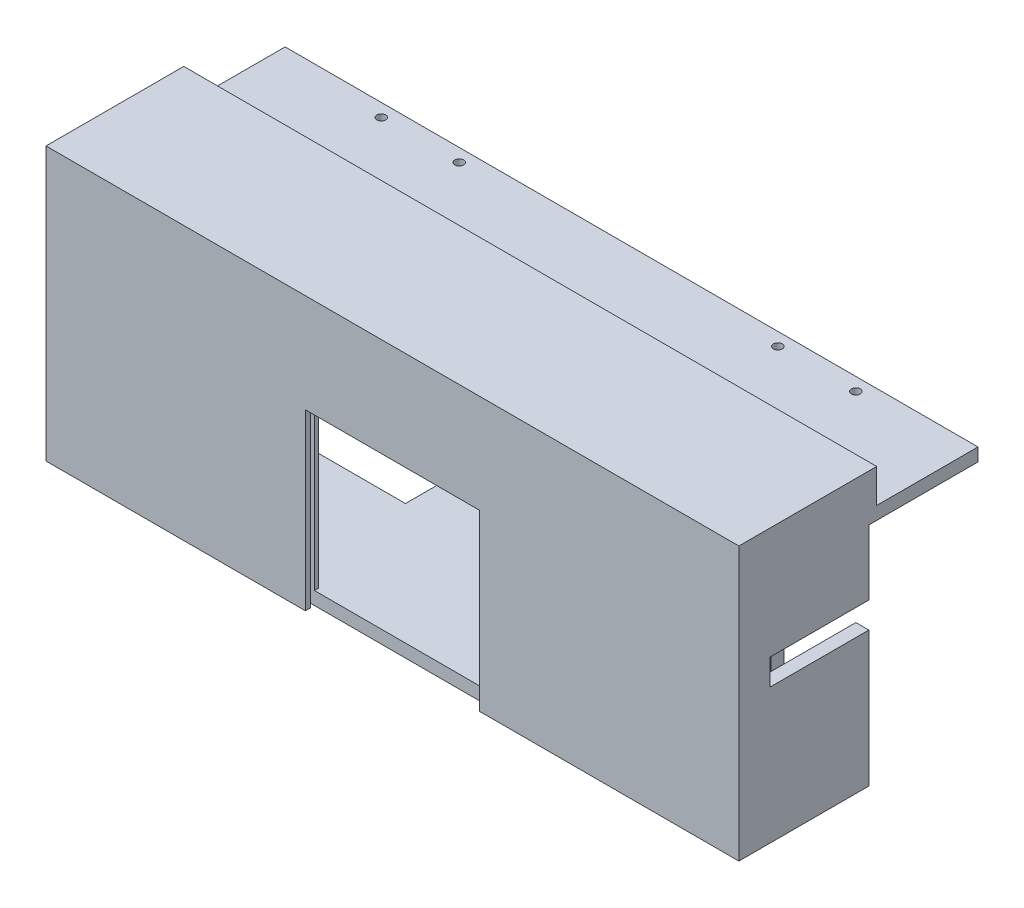
SolidWorks part; units mm, degrees
note: The reader was unsure of these and kept them because the rebuilt part matched: shared geometry of "Sketch1<3>", "Sketch1<4>", "Sketch1<6>", "Sketch1<8>", "Sketch1<9>".
ref_plane "Front Plane" through (0, 0, 0) normal (0, 0, 1) x (1, 0, 0)
ref_plane "Top Plane" through (0, 0, 0) normal (0, 1, 0) x (1, 0, 0)
ref_plane "Right Plane" through (0, 0, 0) normal (1, 0, 0) x (0, 0, -1)
sketch "Sketch1" plane through (0, 0, 0) normal (0, 0, 1) x (-1, 0, 0)
  line L0 (0, 18) -> (266.6, 18)
  line L1 (0, 5) -> (266.6, 5)
  line L2 (266.6, 105) -> (0, 105)
  line L3 (266.6, 105) -> (266.6, 0)
  line L4 (266.6, 0) -> (0, 0)
  line L5 (0, 105) -> (0, 0)
  line L6 (0, 13) -> (266.6, 13)
  line L7 (0, 52.5) -> (266.6, 52.5) construction
  line L9 (0, 100) -> (266.6, 100)
  line L11 (261.6, 5) -> (261.6, 100)
  line L12 (5, 100) -> (5, 5)
  line L16 (99.8, 105) -> (166.8, 105)
  line L17 (99.8, 105) -> (99.8, 38)
  line L18 (99.8, 38) -> (166.8, 38)
  line L19 (166.8, 105) -> (166.8, 38)
  point P18 (133.3, 38)
  point P25 (133.3, 0)
  dimension "D4" = 5
  dimension "D6" = 5
  dimension "D9" = 5
  dimension "D10" = 5
  dimension "D11" = 266.6
  dimension "D8" = 13
  dimension "D12" = 5
  dimension "D2" = 52.5
  dimension "D3" = 67
  dimension "D5" = 67
extrude "Walls" add sketch "Sketch1" along normal blind 50 contours L17 L2 L5 L9 | L2 L19 L9 L3 | L11 L7 L3 L9 | L19 L2 L17 L9 | L7 L11 L0 L3 | L11 L6 L3 L0 | L11 L1 L3 L6 | L1 L5 L4 L3 | L12 L6 L5 L1 | L12 L0 L5 L6 | L7 L5 L0 L12 | L5 L7 L12 L9
extrude "roof" add sketch "Sketch1<3>" against normal blind 5 from surface at 50 starting at face at (-133.3, -52.5, 50)
sketch "Sketch1<3>" plane through (0, 0, 0) normal (0, 0, 1) x (-1, 0, 0) same geometry as "Sketch1"
extrude "spacer" add sketch "Sketch1<4>" against normal blind 42 contours L0 L12 L6 L11 | L12 L0 L5 L6 | L11 L6 L3 L0
sketch "Sketch1<4>" plane through (0, 0, 0) normal (0, 0, 1) x (-1, 0, 0) same geometry as "Sketch1"
sketch "Sketch2" plane through (-266.6, 0, 0) normal (-1, 0, 0) x (0, 0, 1)
  line L0 (0, -105) -> (0, -18) construction
  line L1 (0, -43.0141) -> (38, -43.0141)
  line L2 (0, -43.0141) -> (0, -53.0141)
  line L3 (0, -53.0141) -> (38, -53.0141)
  line L4 (38, -43.0141) -> (38, -53.0141)
  line L5 (50, -105) -> (50, 0) construction
  line L7 (50, -52.5) -> (0, -52.5) construction
  line L8 (50, -105) -> (50, 0) construction
  point P8 (50, -52.5)
  point P13 (38, -48.0141)
  point P14 (38, -58.0018)
  dimension "D1" = 10
  dimension "D2" = 38
  dimension "D3" = 4.4859
extrude "fiber cutout" cut sketch "Sketch2" against normal through all both and the other way through all
sketch "Thorlab rear wall" plane through (0, -13, 0) normal (0, -1, 0) x (1, 0, 0)
  line L1 (-266.6, 0) -> (0, 0)
  line L2 (-266.6, 0) -> (-266.6, -42)
  line L3 (-266.6, -42) -> (0, -42)
  line L4 (0, 0) -> (0, -42)
sketch "Sketch4" plane through (0, -18, 0) normal (0, 1, 0) x (1, 0, 0)
  line L1 (-42, 9) -> (-72, 9) construction
  line L2 (-42, 9) -> (-42, 37) construction
  line L3 (-42, 37) -> (-72, 37) construction
  line L4 (-72, 9) -> (-72, 37) construction
  line L8 (-224.6, 37) -> (-194.6, 37) construction
  line L9 (-224.6, 37) -> (-224.6, 9) construction
  line L10 (-224.6, 9) -> (-194.6, 9) construction
  line L11 (-194.6, 37) -> (-194.6, 9) construction
  point P5 (-42, 9)
  point P6 (-72, 9)
  point P7 (-72, 37)
  point P8 (-42, 37)
  point P429 (-224.6, 37)
  point P432 (-194.6, 37)
  point P435 (-194.6, 9)
  point P438 (-224.6, 9)
  dimension "D1" = 9
  dimension "D2" = 42
  dimension "D3" = 30
  dimension "D4" = 28
  dimension "D5" = 122.6
hole_wizard "M3 Clearance Hole" positions "Sketch4" profile "Sketch5" hole size "M3" standard "ANSI Metric" end condition through all
sketch "Sketch5" plane through (-224.6, -18, -9) normal (1, 0, 0) x (0, 0, -1)
  line L0 (0, 0) -> (0, 18)
  line L1 (0, 18) -> (1.7, 18)
  line L2 (1.7, 18) -> (1.7, 0)
  line L5 (1.7, 0) -> (0, 0)
  line L11 (0, -6.35) -> (0, 107.95) construction
  dimension "Thru Hole Dia." = 3.4
  dimension "Thru Hole Depth" = 18
extrude "rear wall floor" add sketch "Sketch1<6>" against normal blind 3 contours L1 L5 L4 L3 | L12 L6 L5 L1 | L6 L12 L1 L11 | L11 L1 L3 L6
sketch "Sketch1<6>" plane through (0, 0, 0) normal (0, 0, 1) x (-1, 0, 0) same geometry as "Sketch1"
sketch "Sketch6" plane through (0, -105, 0) normal (0, -1, 0) x (1, 0, 0)
  line L0 (-266.6, 50) -> (0, 50) construction
  line L1 (-168.3, 48) -> (-98.3, 48)
  line L2 (-168.3, 48) -> (-168.3, 46.5)
  line L3 (-168.3, 46.5) -> (-98.3, 46.5)
  line L4 (-98.3, 48) -> (-98.3, 46.5)
  point P6 (-133.3, 50)
  point P7 (-133.3, 48)
  dimension "D1" = 2
  dimension "D2" = 1.5
  dimension "D3" = 70
extrude "window through cut" cut sketch "Sketch6" against normal blind 70 and the other way through all
extrude "window slot cut" cut sketch "Sketch1<8>" against normal up to surface (5 mm away) from surface at 50 contours L17 L7 L19 L9 | L7 L17 L18 L19 up to face at (-133.3, -52.5, 45) starting at face at (-133.3, -52.5, 50)
sketch "Sketch1<8>" plane through (0, 0, 0) normal (0, 0, 1) x (-1, 0, 0) same geometry as "Sketch1"
extrude "window edge through cut" cut sketch "Sketch1<9>" against normal up to surface (3.5 mm away) from surface at 50 contours L19 L2 L17 L9 up to face at (-133.3, -69, 46.5) starting at face at (-133.3, -69, 50)
sketch "Sketch1<9>" plane through (0, 0, 0) normal (0, 0, 1) x (-1, 0, 0) same geometry as "Sketch1"
ref_plane "Plane1" through (-133.3, 0, 50) normal (1, 0, 0) x (0, 0, -1)
sketch "Sketch7" plane through (-133.3, 0, 50) normal (1, 0, 0) x (0, 0, -1)
  line L1 (50, -105) -> (50, -53.0141) construction
  line L2 (105.6688, -120) -> (105.6688, -143.4419)
  line L3 (105.6688, -143.4419) -> (100.6688, -143.4419)
  line L4 (100.6688, -143.4419) -> (100.6688, -123.4419)
  line L5 (100.6688, -123.4419) -> (50, -105)
  line L6 (100.6688, -123.4419) -> (91.096, -123.4419) construction
  line L7 (50, -100) -> (50, -105)
  line L8 (50, -100) -> (75.6688, -100)
  line L9 (75.6688, -100) -> (105.6688, -120)
  point P4 (105.5, -100)
  point P12 (105.6688, -100)
  point P14 (0, 0)
  point P15 (0, 0)
  point P16 (0, 0)
  point P17 (105.6688, -113.5055)
  dimension "D1" = 5
  dimension "D2" = 5
  dimension "D3" = 20
  dimension "D5" = 20
  dimension "D6" = 20
  dimension "D4" = 55.6688
  dimension "D7" = 30
extrude "Front leg mounting" add sketch "Sketch7" along normal blind 45 and the other way blind 45
sketch "Sketch8" plane through (0, 0, -50.6688) normal (0, 0, 1) x (1, 0, 0)
  line L0 (-168.3, -105) -> (-98.3, -105) construction
  line L1 (-95.2, -136.4) -> (-171.4, -136.4) construction
  point P0 (-95.2, -136.4)
  point P1 (-171.4, -136.4)
  point P4 (-133.3, -105)
  point P5 (-133.3, -136.4)
  dimension "D1" = 31.4
  dimension "D2" = 38.1
hole_wizard "1/4 Clearance Hole1" positions "Sketch8" profile "Sketch9" hole size "1/4" standard "ANSI Inch" end condition through all
sketch "Sketch9" plane through (-95.2, -136.4, -50.6688) normal (1, 0, 0) x (0, -1, 0)
  line L0 (0, 0) -> (0, 5)
  line L1 (0, 5) -> (3.3782, 5)
  line L2 (3.3782, 5) -> (3.3782, 0)
  line L5 (3.3782, 0) -> (0, 0)
  line L11 (0, -6.35) -> (0, 107.95) construction
  dimension "Thru Hole Dia." = 6.7564
  dimension "Thru Hole Depth" = 5
sketch "Sketch11" plane through (0, -100, 0) normal (0, 1, 0) x (1, 0, 0)
  line L0 (-133.3, -123.315) -> (-133.3, 23.315) construction
  line L1 (-266.6, 0) -> (0, 0) construction
  line L2 (-178.3, 55.6688) -> (-88.3, 55.6688) construction
  line L4 (-146.3, 29.5285) -> (-146.3, 55.6688)
  line L5 (-146.3, 55.6688) -> (-120.3, 55.6688)
  line L6 (-120.3, 29.5285) -> (-120.3, 55.6688)
  line L7 (-146.3, 55.6688) -> (-120.3, 55.6688)
  line L8 (-146.3, 29.5285) -> (-145.0657, 22.5285)
  line L9 (-145.0657, 22.5285) -> (-121.5343, 22.5285)
  line L10 (-121.5343, 22.5285) -> (-120.3, 29.5285)
  line L11 (-120.3, 29.5285) -> (-120.3, 4.8125) construction
  arc A0 (-146.3, 29.5285) -> (-120.3, 29.5285) centre (-133.3, 29.5285) ccw construction
  point P1 (-145.5905, 22.5285)
  point P6 (-133.3, 0)
  line M10 (-88.3, 25.6688) -> (-178.3, 25.6688)
  dimension "D2" = 13
  dimension "D3" = 7
  dimension "D1" = 29.5285
  dimension "D4" = 10
extrude "Front hole cutout" cut sketch "Sketch11" against normal up to surface (43.4419 mm away) contours L10 L6 L5 L4 L8 M10 | L9 L10 L8 M10 up to face at (-133.3, -143.4419, -53.1688)
equation "\"D10@Sketch1\"=\"D9@Sketch1\""
equation "\"D4@Sketch1\"=\"D6@Sketch1\""
equation "\"D12@Sketch1\"=\"D9@Sketch1\""
equation "\"Glass_width\"= 70"
equation "\"D3@Sketch6\"=\"Glass_width\""
equation "\"D5@Sketch1\"=\"Glass_width\"-3"
equation "\"Glass_depth\"=70"
equation "\"D3@Sketch1\"=\"Glass_depth\"-3"
equation "\"roof_thickness\"=5"
equation "\"D1@roof\"=\"roof_thickness\""
equation "\"D2@Sketch7\"=\"D1@Sketch7\""
equation "\"front_wall_thickness\"= 5"
equation "\"D6@Sketch1\"=\"front_wall_thickness\""
equation "\"D1@Sketch7\"=\"front_wall_thickness\""
equation "\"D9@Sketch1\"=\"D6@Sketch1\""
